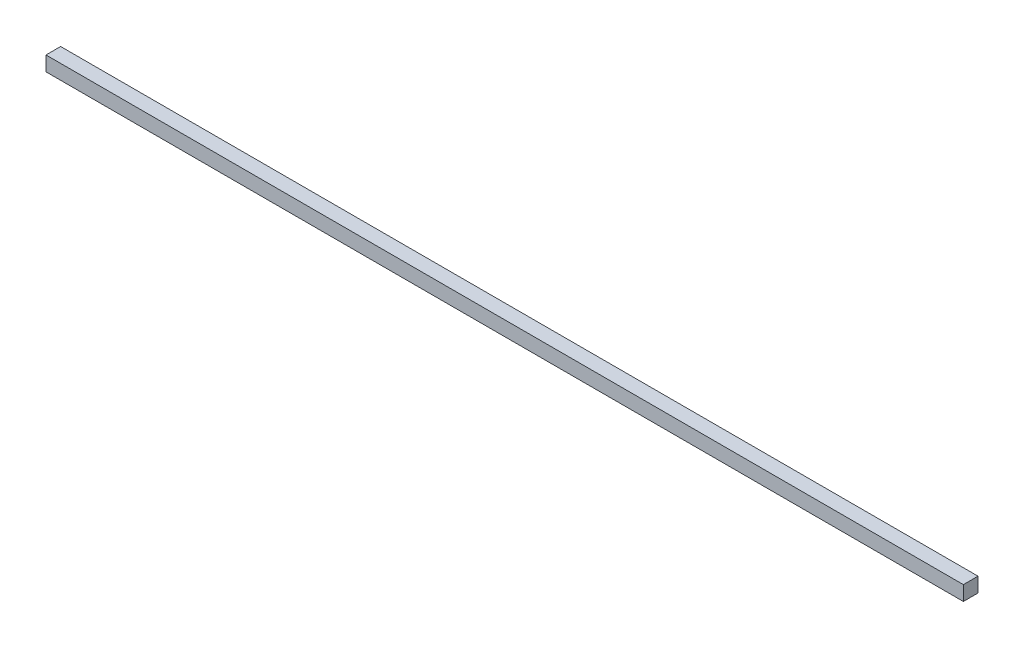
SolidWorks part; units mm, degrees
ref_plane "Front Plane" through (0, 0, 0) normal (0, 0, 1) x (1, 0, 0)
ref_plane "Top Plane" through (0, 0, 0) normal (0, 1, 0) x (1, 0, 0)
ref_plane "Right Plane" through (0, 0, 0) normal (1, 0, 0) x (0, 0, -1)
sketch "Sketch2" plane through (0, 0, 0) normal (1, 0, 0) x (0, 0, -1)
  line L1 (0, 0) -> (4.7625, 0)
  line L2 (0, 0) -> (0, 4.7625)
  line L3 (0, 4.7625) -> (4.7625, 4.7625)
  line L4 (4.7625, 0) -> (4.7625, 4.7625)
  dimension "D1" = 4.7625
extrude "Boss-Extrude1" add sketch "Sketch2" against normal blind 298.45
